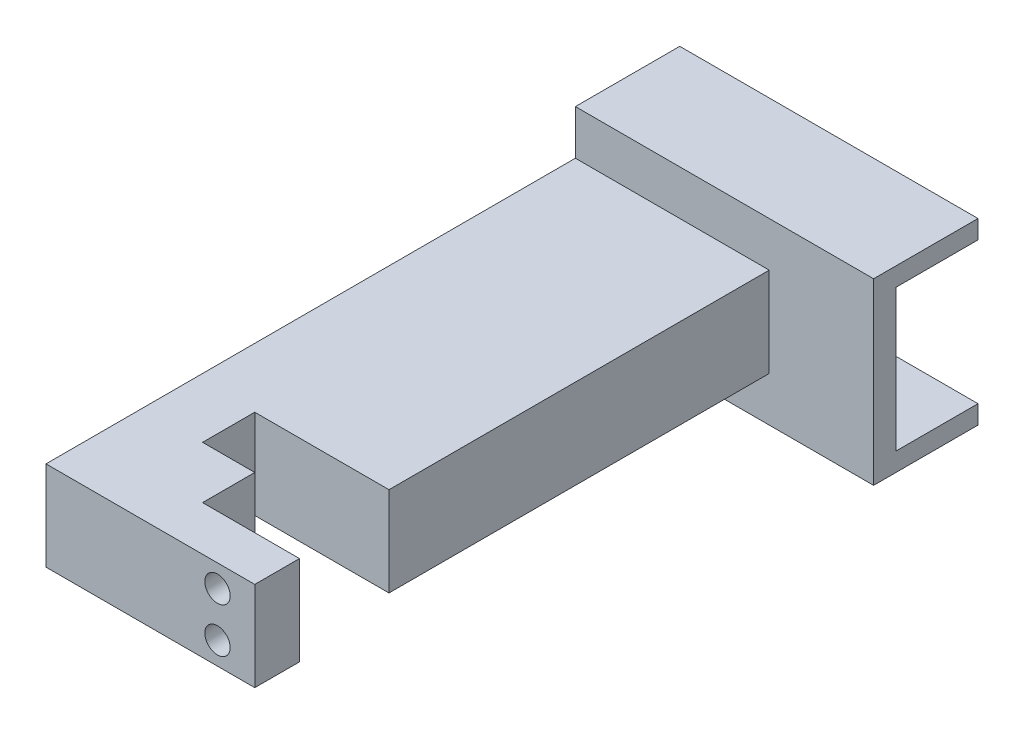
SolidWorks part; units mm, degrees
material "7075-T6 (SN)"
ref_plane "Front Plane" through (0, 0, 0) normal (0, 0, 1) x (1, 0, 0)
ref_plane "Top Plane" through (0, 0, 0) normal (0, 1, 0) x (1, 0, 0)
ref_plane "Right Plane" through (0, 0, 0) normal (1, 0, 0) x (0, 0, -1)
sketch "Sketch1" plane through (0, 0, 0) normal (0, 0, 1) x (1, 0, 0)
  line L1 (-44, -26) -> (-30, -26)
  line L2 (-44, -26) -> (-44, -14)
  line L3 (-44, -14) -> (-30, -14)
  line L4 (-30, -26) -> (-30, -14)
  circle A0 centre (-35, -23) radius 1.7
  circle A1 centre (-35, -17) radius 1.7
extrude "Outboard_Foot" add sketch "Sketch1" along normal blind 6 from offset 6 offset against normal yes
sketch "Sketch2" plane through (0, 0, 0) normal (0, 0, 1) x (1, 0, 0)
  line L1 (-44, -26) -> (-32, -26)
  line L2 (-44, -26) -> (-44, -14)
  line L3 (-44, -14) -> (-32, -14)
  line L4 (-32, -26) -> (-32, -14)
extrude "Drop_Web" add sketch "Sketch2" along normal blind 69.5 from offset 71 offset against normal yes
sketch "Sketch3" plane through (0, 0, 0) normal (0, 0, 1) x (1, 0, 0)
  line L1 (-58, -32) -> (-18, -32)
  line L2 (-58, -32) -> (-58, -8)
  line L3 (-58, -8) -> (-18, -8)
  line L4 (-18, -32) -> (-18, -8)
extrude "Cross_Slot_Block" add sketch "Sketch3" along normal blind 14 from offset 85 offset against normal yes
sketch "Sketch4" plane through (0, 0, 0) normal (1, 0, 0) x (0, 0, -1)
  line L0 (82, -29.51) -> (82, -10.49)
  line L1 (82, -10.49) -> (74, -10.49)
  line L2 (74, -10.49) -> (74, -29.51)
  line L3 (74, -29.51) -> (82, -29.51)
extrude "X_Floating_Y_Driven_Slot" cut sketch "Sketch4" against normal through all and the other way through all
sketch "Sketch5" plane through (0, 0, 0) normal (0, 0, 1) x (1, 0, 0)
  line L1 (-58, -26) -> (-44, -26)
  line L2 (-58, -26) -> (-58, -14)
  line L3 (-58, -14) -> (-44, -14)
  line L4 (-44, -26) -> (-44, -14)
extrude "Outboard_Clearance_Web" add sketch "Sketch5" along normal blind 65 from offset 71 offset against normal yes
sketch "Sketch6" plane through (0, 0, 0) normal (0, 1, 0) x (1, 0, 0)
  line L0 (-50, 20) -> (-31, 20)
  line L1 (-31, 20) -> (-31, 13)
  line L2 (-31, 13) -> (-50, 13)
  line L3 (-50, 13) -> (-50, 20)
extrude "Fixed_Base_Ear_Clearance_Cut" cut sketch "Sketch6" against normal through all and the other way through all
sketch "Sketch7" plane through (0, 0, 0) normal (1, 0, 0) x (0, 0, -1)
  line L0 (85.5, -29.51) -> (85.5, -10.49)
  line L1 (85.5, -10.49) -> (74, -10.49)
  line L2 (74, -10.49) -> (74, -29.51)
  line L3 (74, -29.51) -> (85.5, -29.51)
extrude "Slot_Bottom_Upriser_Opening" cut sketch "Sketch7" against normal through all and the other way through all
sketch "Sketch8" plane through (0, 0, 0) normal (0, 0, 1) x (1, 0, 0)
  line L1 (-58, -26) -> (-43, -26)
  line L2 (-58, -26) -> (-58, -14)
  line L3 (-58, -14) -> (-43, -14)
  line L4 (-43, -26) -> (-43, -14)
extrude "Outboard_Foot_Web_Bridge" add sketch "Sketch8" along normal blind 7 from offset 7 offset against normal yes
sketch "Sketch9" plane through (0, 0, 0) normal (0, 1, 0) x (1, 0, 0)
  line L0 (-43, 13.5) -> (-31, 13.5)
  line L1 (-31, 13.5) -> (-31, 6)
  line L2 (-31, 6) -> (-43, 6)
  line L3 (-43, 6) -> (-43, 13.5)
extrude "YDrop_M3_Fastener_Underfoot_Relief" cut sketch "Sketch9" against normal through all and the other way through all
sketch "Sketch10" plane through (0, 0, 0) normal (0, 0, 1) x (1, 0, 0)
  circle A0 centre (-35, -23) radius 1.7
  circle A1 centre (-35, -17) radius 1.7
extrude "YDrop_M3_Through_Recut" cut sketch "Sketch10" against normal blind 6.5
